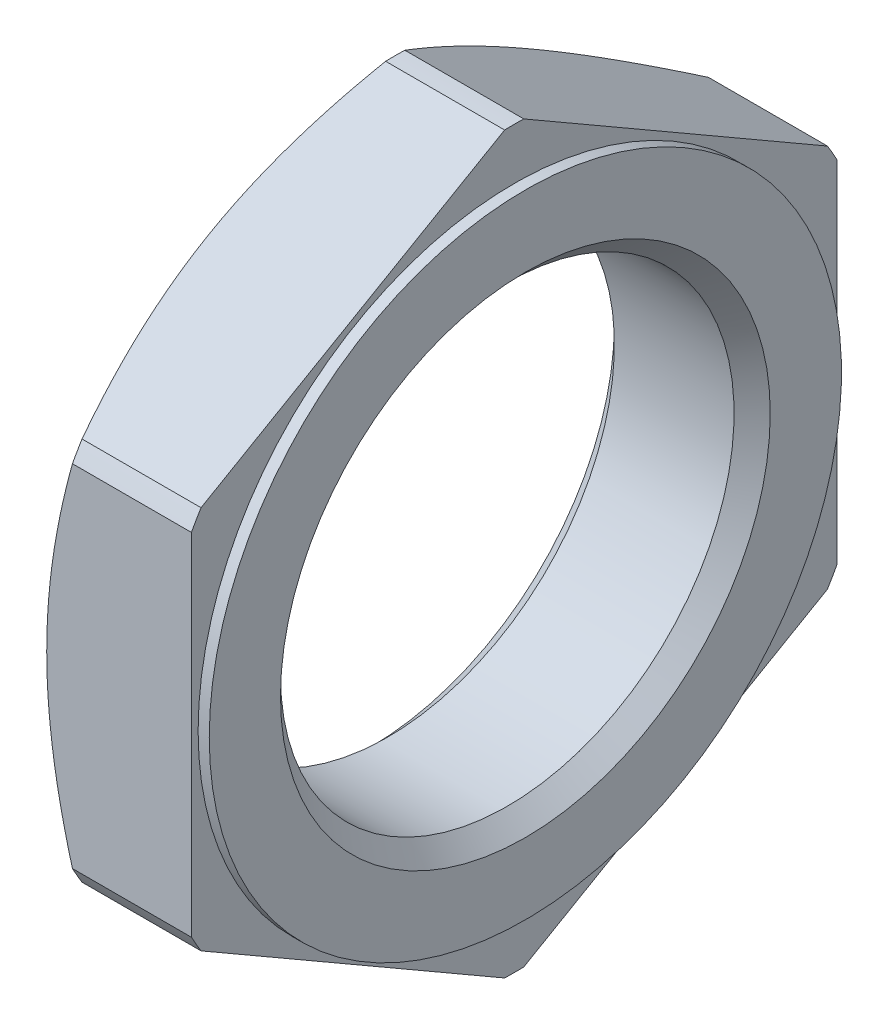
SolidWorks part; units mm, degrees
ref_plane "前视基准面" through (0, 0, 0) normal (0, 0, 1) x (1, 0, 0)
ref_plane "上视基准面" through (0, 0, 0) normal (0, 1, 0) x (1, 0, 0)
ref_plane "右视基准面" through (0, 0, 0) normal (1, 0, 0) x (0, 0, -1)
sketch "草图1" plane through (0, 0, 0) normal (0, 0, 1) x (1, 0, 0)
  line L0 (0, 0) -> (0, 14.5)
  line L1 (0, 14.5) -> (1.1547, 16.5)
  line L2 (1.1547, 16.5) -> (6.5, 16.5)
  line L3 (6.5, 16.5) -> (6.5, 14.2)
  line L4 (6.5, 14.2) -> (7, 14.2)
  line L5 (7, 14.2) -> (7, 0)
  line L6 (7, 0) -> (0, 0)
  line L7 (7, 0) -> (0, 0) construction
revolve "旋转1" add sketch "草图1" angle 360 about L7 reverse direction yes
sketch "草图2" plane through (0, 0, 0) normal (0, 0, 1) x (1, 0, 0)
  line L0 (0, 0) -> (0, 11)
  line L1 (0, 11) -> (0.812, 10.188)
  line L2 (0.812, 10.188) -> (6.188, 10.188)
  line L3 (6.188, 10.188) -> (7, 11)
  line L4 (7, 11) -> (7, 0)
  line L5 (7, 0) -> (0, 0)
  line L6 (7, 0) -> (0, 0) construction
revolve "切除-旋转1" cut sketch "草图2" angle 360 about L6 reverse direction yes
cosmetic thread "装饰螺纹线1" parameters "D1"=7, "D2"=22
sketch "草图3" plane through (0, 0, 0) normal (1, 0, 0) x (0, 0, -1)
  line L0 (-29, 29) -> (-29, -29)
  line L1 (-29, -29) -> (29, -29)
  line L2 (29, -29) -> (29, 29)
  line L3 (29, 29) -> (-29, 29)
  line L4 (-14.5, -8.3716) -> (0, -16.7432)
  line L5 (0, -16.7432) -> (14.5, -8.3716)
  line L6 (14.5, -8.3716) -> (14.5, 8.3716)
  line L7 (14.5, 8.3716) -> (0, 16.7432)
  line L8 (0, 16.7432) -> (-14.5, 8.3716)
  line L9 (-14.5, 8.3716) -> (-14.5, -8.3716)
extrude "切除-拉伸1" cut sketch "草图3" along normal blind 7
ref_plane "基准面4" through (3.5, 0, 0) normal (1, 0, 0) x (0, 0, -1)
ref_plane "基准面5" through (7, 0, 0) normal (1, 0, 0) x (0, 0, -1)
ref_plane "nut XY" through (3.5, 0, 0) normal (-1, 0, 0) x (0, 0, 1)
ref_plane "nut XZ" through (0, 0, 0) normal (0, 1, 0) x (1, 0, 0)
ref_plane "nut YZ" through (0, 0, 0) normal (0, 0, -1) x (-1, 0, 0)
ref_axis "nut X" through (3.5, 0, 80.9) along (0, 0, -1)
ref_axis "nut Y" through (3.5, 50, 0) along (0, -1, 0)
ref_axis "nut Z" through (-80.9, 0, 0) along (1, 0, 0)
sketch3d "nut"
  point P0 (3.5, 0, 0)
ref_plane "nut1 XY" through (7, 0, 0) normal (-1, 0, 0) x (0, 0, 1)
ref_plane "nut1 XZ" through (0, 0, 0) normal (0, 1, 0) x (1, 0, 0)
ref_plane "nut1 YZ" through (0, 0, 0) normal (0, 0, -1) x (-1, 0, 0)
ref_axis "nut1 X" through (7, 0, 80.9) along (0, 0, -1)
ref_axis "nut1 Y" through (7, 50, 0) along (0, -1, 0)
ref_axis "nut1 Z" through (-80.9, 0, 0) along (1, 0, 0)
sketch3d "nut1"
  point P0 (7, 0, 0)
